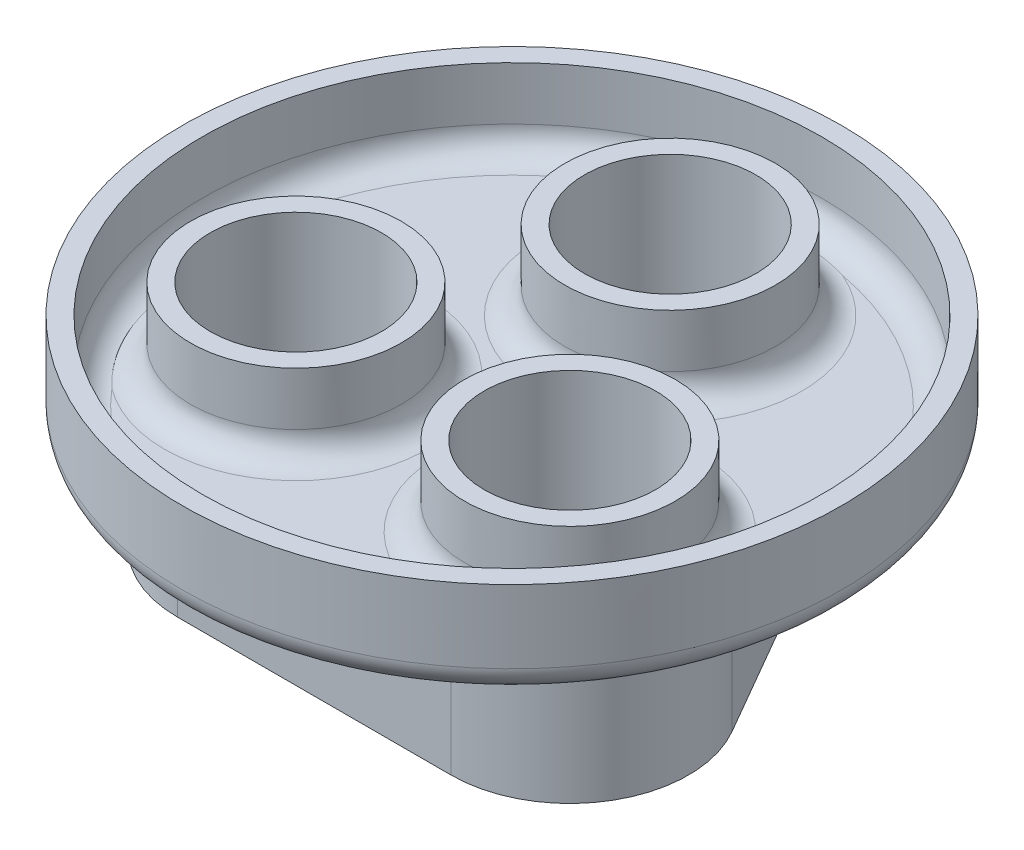
SolidWorks part; units mm, degrees
material "Plain Carbon Steel"
ref_plane "Front Plane" through (0, 0, 0) normal (0, 0, 1) x (1, 0, 0)
ref_plane "Top Plane" through (0, 0, 0) normal (0, 1, 0) x (1, 0, 0)
ref_plane "Right Plane" through (0, 0, 0) normal (1, 0, 0) x (0, 0, -1)
sketch "Sketch1" plane through (0, 0, 0) normal (0, 1, 0) x (1, 0, 0)
  line L0 (-92.3876, -7.62) -> (-39.5947, 83.82)
  line L1 (39.5947, 83.82) -> (92.3876, -7.62)
  line L2 (52.7929, -76.2) -> (-52.7929, -76.2)
  circle A0 centre (0, 0) radius 60.96 construction
  circle A1 centre (0, 0) radius 127
  circle A2 centre (0, 60.96) radius 45.72
  circle A3 centre (0, 60.96) radius 33.02
  circle A4 centre (52.7929, -30.48) radius 45.72
  circle A5 centre (52.7929, -30.48) radius 33.02
  circle A6 centre (-52.7929, -30.48) radius 45.72
  circle A7 centre (-52.7929, -30.48) radius 33.02
  point P16 (0, 0)
  dimension "D1" = 121.92
  dimension "D2" = 254
  dimension "D3" = 66.04
  dimension "D4" = 91.44
  dimension "D5" = 3
extrude "Boss-Extrude3" add sketch "Sketch1" along normal blind 38.1 contours A1 A6 L0 A2 L1 A4 L2 | A6 L2 A4 L1 A2 L0 | A6 A7 | A2 A3 | A4 A5 region at (0, 0, 0) region at (-41.2944, 0, -12.433) region at (0, 0, -105.3868) region at (14.3181, 0, 8.2666) region at (-123.4079, 0, 0)
shell "Shell5" thickness 7.62 removed face at (0, 38.1, 127)
extrude "Boss-Extrude6" add sketch "Sketch1<5>" against normal blind 50.8 separate body contours A6 L2 A4 L1 A2 L0 | A2 A3 | A6 A7 | A4 A5 region at (0, 0, 0) region at (-41.2944, 0, -12.433) region at (0, 0, -105.3868) region at (14.3181, 0, 8.2666)
sketch "Sketch1<5>" plane through (0, 0, 0) normal (0, 1, 0) x (1, 0, 0) same geometry as "Sketch1"
shell "Shell6" thickness 7.62 removed face at (0, -50.8, 0)
combine bodies "Combine1" operation type add bodies to combine 106 103
fillet "Fillet1" radius 10 16 edges at (0, -7.62, 68.58) (17.5976, -7.62, 10.16) (59.392, -7.62, -34.29) (0, -7.62, -20.32) (-59.392, -7.62, -34.29) (-17.5976, -7.62, 10.16) (-52.7929, 7.62, 71.12) (0, 7.62, -20.32) (52.7929, 7.62, 71.12) (0, 7.62, 119.38) (-38.6508, -29.21, 68.58) (-78.7174, -29.21, -0.8174) (38.6508, -29.21, 68.58) (-40.0666, -29.21, -67.7626) (40.0666, -29.21, -67.7626) (78.7174, -29.21, -0.8174)
fillet "Fillet2" radius 10 7 edges at (0, 0, -106.68) (65.9911, 0, -38.1) (92.3876, 0, 53.34) (0, 0, 76.2) (-92.3876, 0, 53.34) (-65.9911, 0, -38.1) (0, 0, 127)
